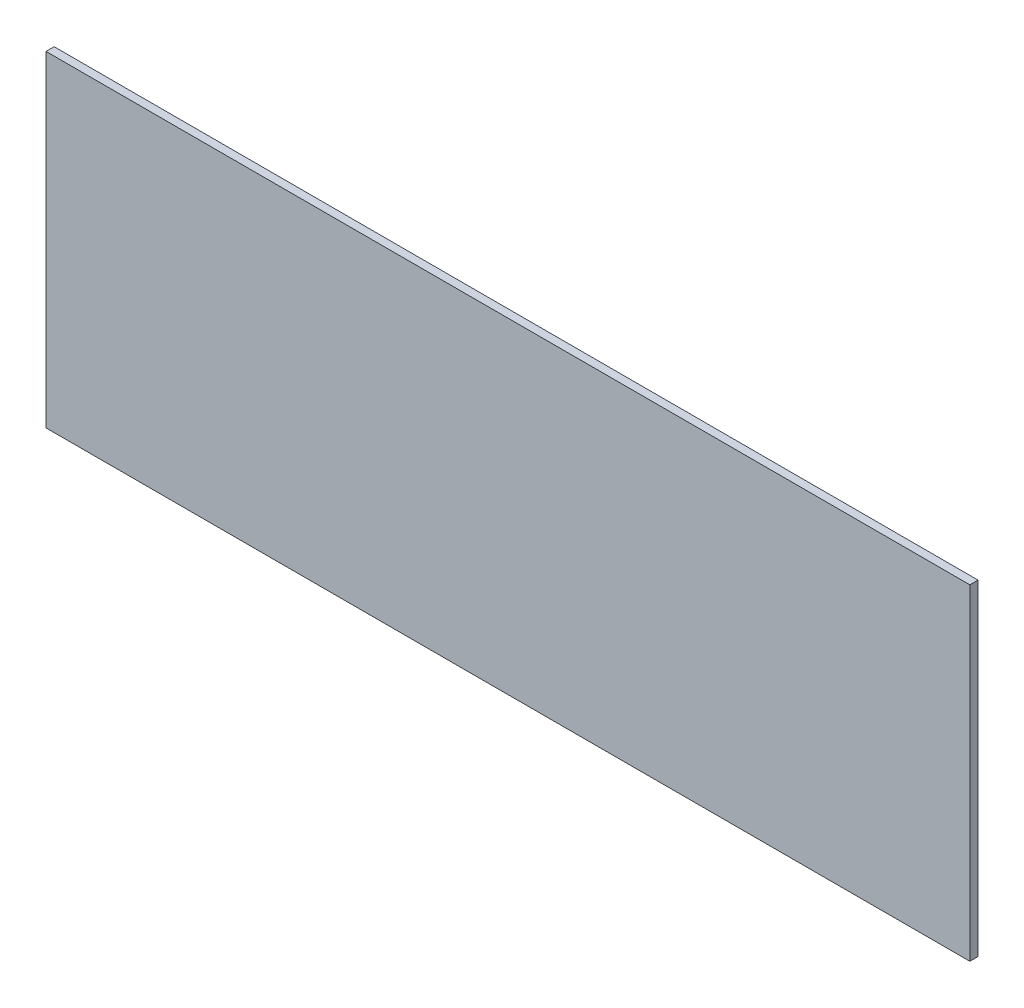
SolidWorks part; units mm, degrees
material "AISI 316 Chapa de acero inoxidable (SS)"
ref_plane "Alzado" through (0, 0, 0) normal (0, 0, 1) x (1, 0, 0)
ref_plane "Planta" through (0, 0, 0) normal (0, 1, 0) x (1, 0, 0)
ref_plane "Vista lateral" through (0, 0, 0) normal (1, 0, 0) x (0, 0, -1)
sketch "Croquis1" plane through (0, 0, 0) normal (0, 0, 1) x (1, 0, 0)
  line L1 (-85, -30) -> (85, -30)
  line L2 (-85, -30) -> (-85, 30)
  line L3 (-85, 30) -> (85, 30)
  line L4 (85, -30) -> (85, 30)
  line L5 (-85, -30) -> (85, 30) construction
  line L6 (-85, 30) -> (85, -30) construction
  point P0 (0, 0)
  dimension "D1" = 60
  dimension "D2" = 170
extrude "Saliente-Extruir1" add sketch "Croquis1" along normal blind 1.5
